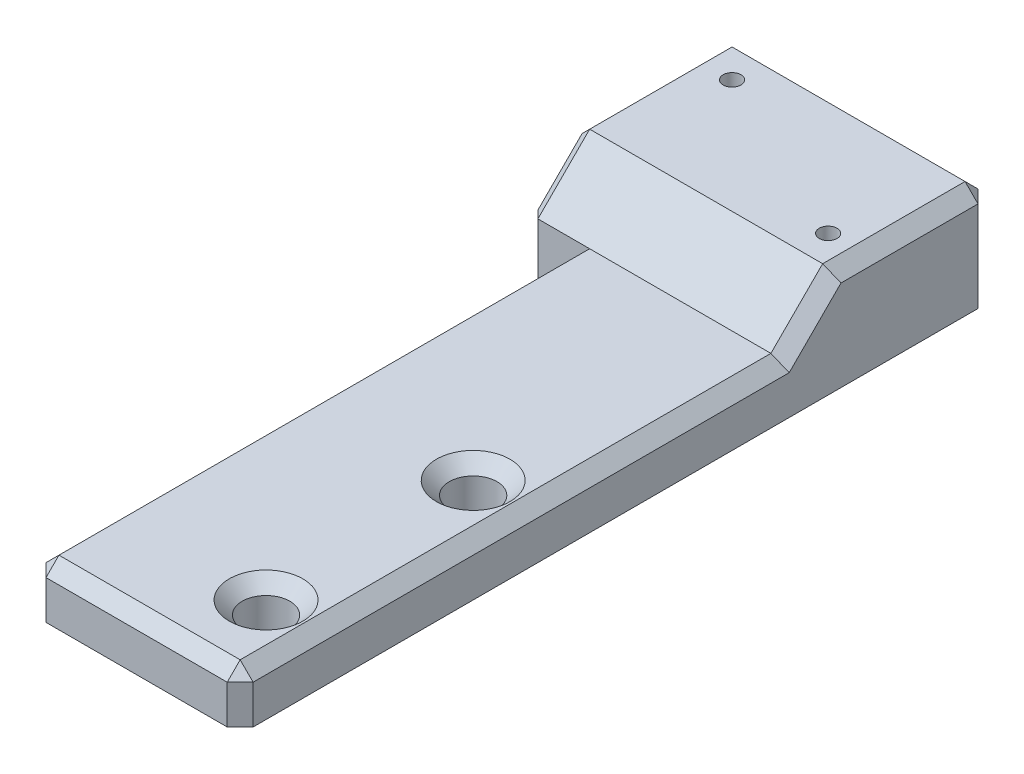
SolidWorks part; units mm, degrees
ref_plane "Front Plane" through (0, 0, 0) normal (0, 0, 1) x (1, 0, 0)
ref_plane "Top Plane" through (0, 0, 0) normal (0, 1, 0) x (1, 0, 0)
ref_plane "Right Plane" through (0, 0, 0) normal (1, 0, 0) x (0, 0, -1)
sketch "Sketch1" plane through (0, 0, 0) normal (0, 1, 0) x (1, 0, 0)
  line L1 (0, 0) -> (31.75, 0)
  line L2 (0, 0) -> (0, 92.075)
  line L3 (0, 92.075) -> (31.75, 92.075)
  line L4 (31.75, 0) -> (31.75, 92.075)
  circle A0 centre (25.4, 9.525) radius 2.921
  circle A1 centre (25.4, 34.925) radius 2.921
  dimension "D3" = 5.842
  dimension "D1" = 31.75
  dimension "D2" = 6.35
  dimension "0.375" = 9.525
  dimension "D4" = 25.4
  dimension "D5" = 57.15
extrude "Boss-Extrude1" add sketch "Sketch1" along normal blind 12.7
sketch "Sketch2" plane through (31.75, 0, 0) normal (1, 0, 0) x (0, 0, -1)
  line L0 (92.075, 12.7) -> (92.075, 0) construction
  line L1 (0, 12.7) -> (66.675, 12.7)
  line L2 (0, 12.7) -> (0, 6.35)
  line L3 (0, 6.35) -> (66.675, 6.35)
  line L4 (66.675, 12.7) -> (66.675, 6.35)
  dimension "D1" = 25.4
  dimension "D2" = 6.35
extrude "Cut-Extrude1" cut sketch "Sketch2" against normal through all
sketch "Sketch3" plane through (0, 0, 0) normal (0, -1, 0) x (1, 0, 0)
  line L0 (0, -92.075) -> (0, 0) construction
  line L2 (31.75, -92.075) -> (0, -92.075) construction
  line L3 (0, 0) -> (6.35, 0)
  line L4 (0, 0) -> (0, -66.675)
  line L5 (0, -66.675) -> (6.35, -66.675)
  line L6 (6.35, 0) -> (6.35, -66.675)
  circle A0 centre (27.2796, -76.581) radius 1.0922
  circle A1 centre (5.08, -86.995) radius 1.0922
  dimension "D1" = 2.1844
  dimension "D2" = 22.1996
  dimension "D3" = 5.08
  dimension "D4" = 5.08
  dimension "D5" = 6.35
  dimension "D6" = 10.414
  dimension "2.625" = 66.675
extrude "Cut-Extrude2" cut sketch "Sketch3" against normal through all
chamfer "Chamfer1" distance 6.35 angle 45 1 edges at (15.875, 12.7, -66.675)
chamfer "Chamfer2" distance 1.5875 angle 45 15 edges at (25.4, 6.35, -12.446) (25.4, 6.35, -37.846) (31.75, 6.35, -92.075) (31.75, 3.175, 0) (6.35, 3.175, 0) (6.35, 6.35, -33.3375) (19.05, 6.35, 0) (31.75, 6.35, -33.3375) (31.75, 9.525, -69.85) (31.75, 12.7, -82.55) (0, 6.35, -92.075) (15.875, 12.7, -92.075) (0, 12.7, -82.55) (0, 9.525, -69.85) (0, 3.175, -66.675)
